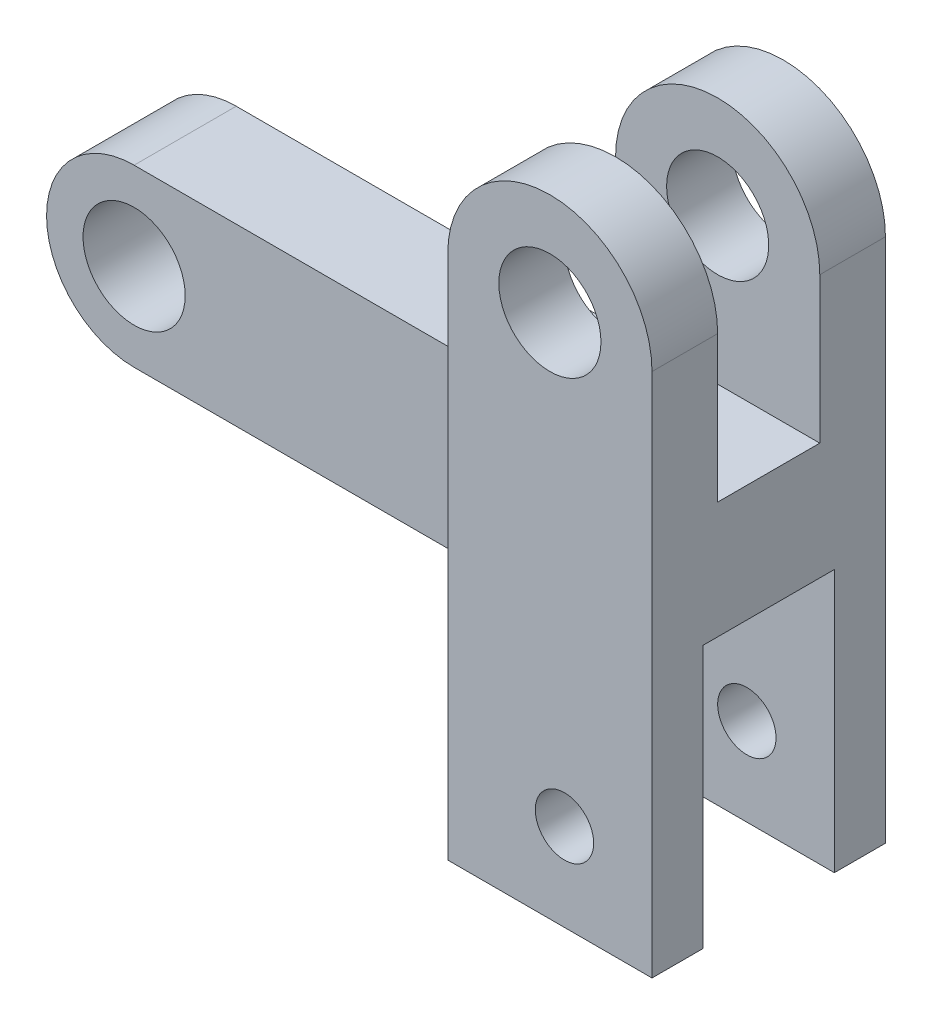
SolidWorks part; units mm, degrees
ref_plane "前视基准面" through (0, 0, 0) normal (0, 0, 1) x (1, 0, 0)
ref_plane "上视基准面" through (0, 0, 0) normal (0, 1, 0) x (1, 0, 0)
ref_plane "右视基准面" through (0, 0, 0) normal (1, 0, 0) x (0, 0, -1)
other "Configuration Table"
sketch "草图1" plane through (0, 0, 0) normal (0, 1, 0) x (1, 0, 0)
  line L1 (0, 3.5) -> (7, 3.5)
  line L2 (0, -3.5) -> (7, -3.5)
  line L3 (0, 3.5) -> (7, 3.5) construction
  line L4 (7, 3.5) -> (7, -3.5)
  line L5 (0, 3.5) -> (0, -3.5)
  dimension "D1" = 7
  dimension "D4" = 90
  dimension "D5" = 7
extrude "凸台-拉伸1" add sketch "草图1" along normal blind 2.4
sketch "草图10" plane through (0, 0, -3.5) normal (0, 0, -1) x (-1, 0, 0)
  line L3 (-7, 2.4) -> (0, 2.4) construction
  line L6 (-7, 2.4) -> (0, 2.4)
  line L7 (0, 2.4) -> (0, 10)
  line L9 (-7, 10) -> (-7, 2.4)
  line L10 (0, 2.4) -> (0, 0) construction
  arc A1 (0, 10) -> (-7, 10) centre (-3.5, 10) ccw
  line M3 (0, 2.4) -> (-7, 2.4)
  dimension "D8" = 3.5
  dimension "D9" = 10
extrude "凸台-拉伸6" add sketch "草图10" against normal blind 1.75 contours L7 A1 L9 M3 region at (3.5, 7.6039, -3.5)
extrude "凸台-拉伸8" add sketch "草图10<2>" along normal blind 1.75 from offset 7 contours L7 A1 L9 M3 region at (3.5, 7.6039, -3.5) offset against normal yes
sketch "草图10<2>" plane through (0, 0, -3.5) normal (0, 0, -1) x (-1, 0, 0) same geometry as "草图10"
sketch "草图11" plane through (0, 0, -3.5) normal (0, 0, -1) x (-1, 0, 0)
  circle A2 centre (-3.5, 10) radius 1.75
  dimension "D3" = 3.5
extrude "切除-拉伸1" cut sketch "草图11" against normal through all
sketch "草图17" plane through (0, 0, 0) normal (0, -1, 0) x (1, 0, 0)
  line L6 (0, 3.5) -> (0, -3.5)
  line L7 (0, -3.5) -> (7, -3.5)
  line L8 (7, -3.5) -> (7, 3.5)
  line L9 (7, 3.5) -> (0, 3.5)
  line L12 (0, 3.5) -> (0, -3.5)
  line L13 (0, -3.5) -> (7, -3.5)
  line L14 (7, -3.5) -> (7, 3.5)
  line L15 (7, 3.5) -> (0, 3.5)
  dimension "D1" = 0
extrude "凸台-拉伸10" add sketch "草图17" along normal blind 8
sketch "草图15" plane through (0, 0, 0) normal (0, 0, 1) x (1, 0, 0)
  line L2 (7, 5) -> (7, -1)
  line L10 (7, 10) -> (7, -8) construction
  line L14 (-13, 5) -> (7, 5)
  line L15 (7, 10) -> (7, -8) construction
  line L17 (7, 2.4) -> (7.3779, 2.4)
  line L18 (0, 2.4) -> (7, 2.4) construction
  line L19 (-13, -1) -> (7, -1)
  line L20 (7, -8) -> (0, -8) construction
  arc A0 (-13, -1) -> (-13, 5) centre (-13, 2) cw
  circle A1 centre (-13, 2) radius 1.75
  dimension "D3" = 3.5
  dimension "D1" = 3
  dimension "D2" = 7
  dimension "D4" = 20
extrude "凸台-拉伸9" add sketch "草图15" along normal mid plane 3.5 contours A0 L19 L2 L14 A1 region at (-3.5072, 2, 0)
sketch "草图12" plane through (0, 4, 3.5) normal (0, 0, -1) x (1, 0, 0)
  line L0 (0, 12) -> (7, 12) construction
  line L2 (7, -6) -> (7, 12) construction
  circle A0 centre (4, 9) radius 1
  dimension "D2" = 2
  dimension "D1" = 3
  dimension "D3" = 3
extrude "切除-拉伸2" cut sketch "草图12" along normal through all
sketch "草图18" plane through (7.4, -8, 0) normal (0, 1, 0) x (1, 0, 0)
  line L0 (-0.4, 1.75) -> (-0.4, 3.5) construction
  line L11 (-7.4, -2.25) -> (-0.4, -2.25)
  line L12 (-7.4, -2.25) -> (-7.4, 2.25)
  line L13 (-7.4, 2.25) -> (-0.4, 2.25)
  line L14 (-0.4, -2.25) -> (-0.4, 2.25)
  point P4 (-7.4, 0)
  dimension "D1" = 4.5
  dimension "D2" = 7
extrude "切除-拉伸4" cut sketch "草图18" along normal blind 9
sketch "草图19" plane through (0, 0, 3.5) normal (0, 0, 1) x (1, 0, 0)
  line L4 (0, 10) -> (0, -8)
  line L5 (0, -8) -> (7, -8)
  line L6 (7, -8) -> (7, 10)
  line L8 (0, 10) -> (0, -8)
  line L9 (0, -8) -> (7, -8)
  line L10 (7, -8) -> (7, 10)
  circle A0 centre (4, -5) radius 1 construction
  circle A1 centre (4, -5) radius 1
  circle A2 centre (3.5, 10) radius 1.75 construction
  arc A3 (7, 10) -> (0, 10) centre (3.5, 10) ccw
  arc A4 (7, 10) -> (0, 10) centre (3.5, 10) ccw
  circle A5 centre (3.5, 10) radius 1.75
  dimension "D1" = 0
extrude "凸台-拉伸11" add sketch "草图19" along normal blind 0.5
sketch "草图20" plane through (0, 0, -3.5) normal (0, 0, -1) x (-1, 0, 0)
  line L4 (-7, 10) -> (-7, -8)
  line L5 (-7, -8) -> (0, -8)
  line L6 (0, -8) -> (0, 10)
  line L8 (-7, 10) -> (-7, -8)
  line L9 (-7, -8) -> (0, -8)
  line L10 (0, -8) -> (0, 10)
  circle A0 centre (-4, -5) radius 1 construction
  circle A1 centre (-4, -5) radius 1
  circle A2 centre (-3.5, 10) radius 1.75 construction
  arc A3 (0, 10) -> (-7, 10) centre (-3.5, 10) ccw
  arc A4 (0, 10) -> (-7, 10) centre (-3.5, 10) ccw
  circle A5 centre (-3.5, 10) radius 1.75
  dimension "D1" = 0
extrude "凸台-拉伸12" add sketch "草图20" along normal blind 0.5
